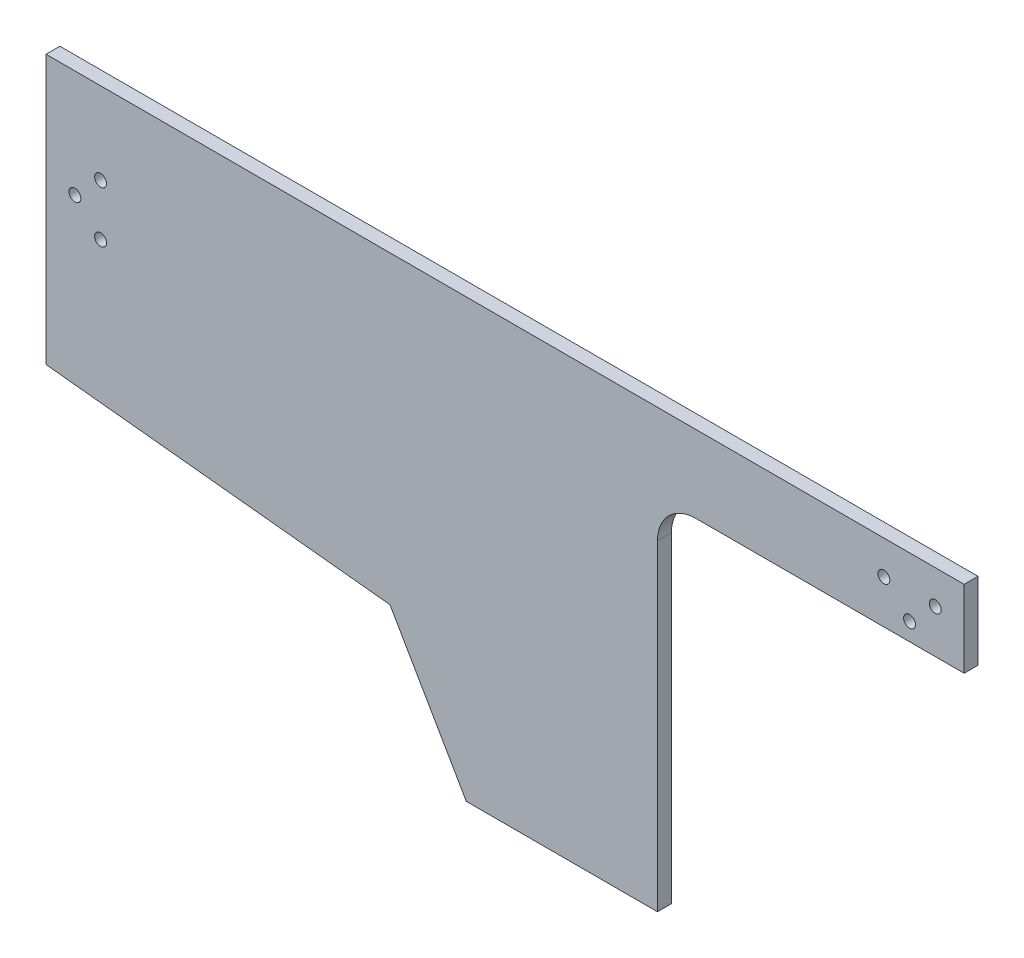
SolidWorks part; units mm, degrees
material "Acrylic (Medium-high impact)"
ref_plane "Front" through (0, 0, 0) normal (0, 0, 1) x (1, 0, 0)
ref_plane "Top" through (0, 0, 0) normal (0, 1, 0) x (1, 0, 0)
ref_plane "Right" through (0, 0, 0) normal (1, 0, 0) x (0, 0, -1)
ref_axis "side-side" through (80.9, 0, 0) along (-1, 0, 0)
ref_axis "up-down" through (0, 50, 0) along (0, -1, 0)
ref_axis "front-back" through (0, 0, -80.9) along (0, 0, 1)
sketch "Sketch1" plane through (0, 0, 0) normal (0, 0, 1) x (1, 0, 0)
  line L0 (-144, 0) -> (-144, 256)
  line L1 (-144, 0) -> (-144, 256) construction
  line L2 (47.48, 163.9531) -> (47.48, 126.6475) construction
  line L3 (47.48, 175) -> (47.48, 74.9035)
  line L4 (-12.0774, 74.9035) -> (-35.8425, 116.0657)
  line L5 (-35.8425, 116.0657) -> (-143, 127.289)
  line L6 (-31.7628, 95.529) -> (-143.0054, 107.1801) construction
  line L7 (143, 211) -> (-143, 211)
  line L8 (143.318, 256) -> (-143.318, 256) construction
  line L9 (144, 0) -> (144, 256)
  line L10 (144, 0) -> (144, 256) construction
  line L11 (59.48, 187) -> (143, 187)
  line L12 (143, 187) -> (143, 211)
  line L13 (143, 0) -> (143, 256) construction
  line L14 (-143, 127.289) -> (-143, 211)
  line L15 (-143, 0) -> (-143, 256) construction
  line L16 (-12.0774, 74.9035) -> (47.48, 74.9035)
  line L17 (42.4, 82.9035) -> (5.32, 82.9035) construction
  line L18 (0.24, 108.7312) -> (-24.74, 40.128) construction
  arc A0 (47.48, 175) -> (59.48, 187) centre (59.48, 175) cw
  circle A1 centre (-134, 177.5) radius 1.85 construction
  circle A2 centre (-126, 169.5) radius 1.85 construction
  circle A3 centre (-126, 185.5) radius 1.85 construction
  circle A4 centre (-134, 177.5) radius 1.85
  circle A5 centre (-126, 169.5) radius 1.85
  circle A6 centre (-126, 185.5) radius 1.85
  circle A7 centre (118, 200.5) radius 1.85 construction
  circle A8 centre (126, 192.5) radius 1.85 construction
  circle A9 centre (134, 200.5) radius 1.85 construction
  circle A10 centre (118, 200.5) radius 1.85
  circle A11 centre (126, 192.5) radius 1.85
  circle A12 centre (134, 200.5) radius 1.85
  dimension "D8" = 12
  dimension "D1" = 20
  dimension "D2" = 45
  dimension "D3" = 24
  dimension "D6" = 8
  dimension "D7" = 60
  dimension "D4" = 1
  dimension "D5" = 1
extrude "Boss-Extrude1" add sketch "Sketch1" along normal blind 4.318
